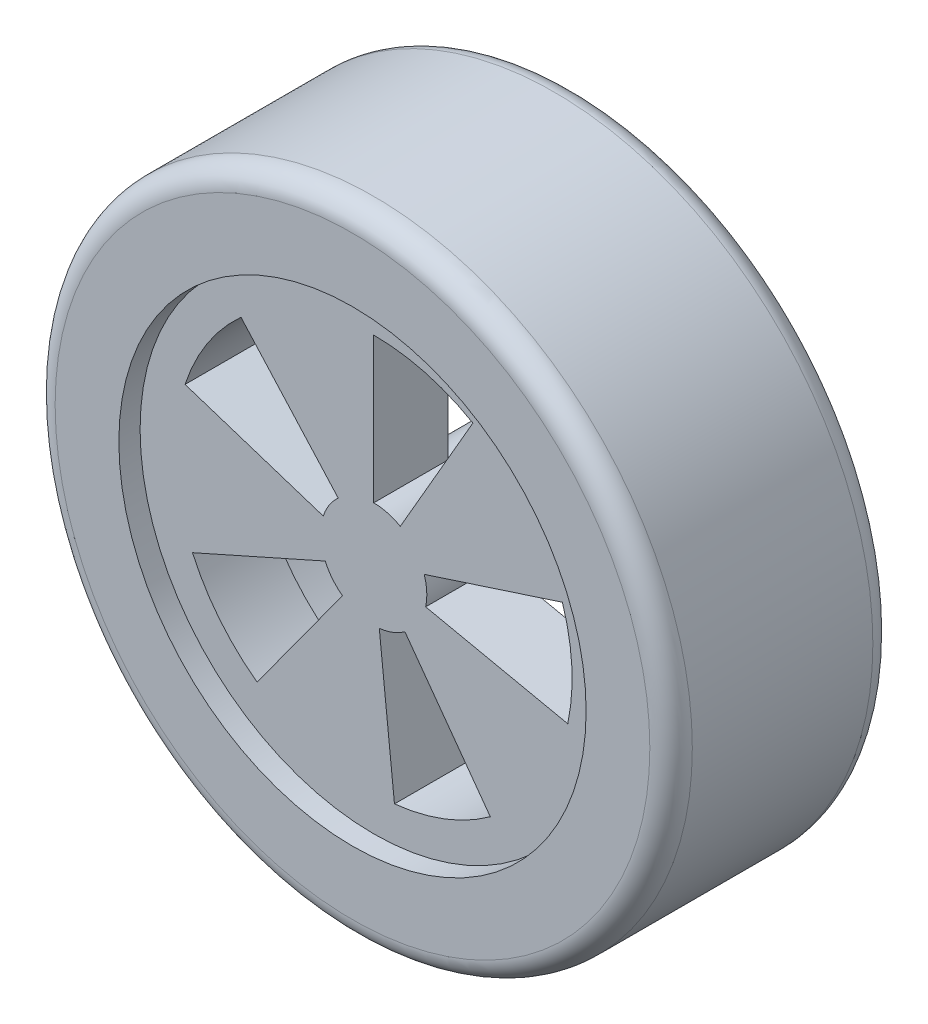
SolidWorks part; units mm, degrees
ref_plane "Front Plane" through (0, 0, 0) normal (0, 0, 1) x (1, 0, 0)
ref_plane "Top Plane" through (0, 0, 0) normal (0, 1, 0) x (1, 0, 0)
ref_plane "Right Plane" through (0, 0, 0) normal (1, 0, 0) x (0, 0, -1)
sketch "Sketch1" plane through (0, 0, 0) normal (0, 0, 1) x (1, 0, 0)
  circle A0 centre (0, 0) radius 15
extrude "Boss-Extrude1" add sketch "Sketch1" along normal blind 10.5 contours A0
sketch "Sketch2" plane through (0, 0, 10.5) normal (0, 0, 1) x (1, 0, 0)
  circle A0 centre (0, 0) radius 11
extrude "Cut-Extrude1" cut sketch "Sketch2" against normal blind 1
sketch "Sketch3" plane through (0, 0, 0) normal (0, 0, -1) x (-1, 0, 0)
  circle A0 centre (0, 0) radius 12
  circle A1 centre (0, 0) radius 2.5
  circle A2 centre (0, 0) radius 1
extrude "Cut-Extrude2" cut sketch "Sketch3" against normal blind 6 contours A0 A1 | A2 region at (11.6606, 0, 0) region at (0, 0, 0)
extrude "Boss-Extrude2" add sketch "Sketch3<4>" along normal blind 2.5 contours A1 A2 region at (2.4293, 0, 0)
sketch "Sketch3<4>" plane through (0, 0, 0) normal (0, 0, -1) x (-1, 0, 0) same geometry as "Sketch3"
fillet "Fillet1" radius 1 2 edges at (15, 0, 0) (15, 0, 10.5)
sketch "Sketch4" plane through (0, 0, 9.5) normal (0, 0, 1) x (1, 0, 0)
  line L0 (0, 2.5) -> (0, 9.3396)
  line L1 (1.25, 2.1651) -> (4.6698, 8.0883)
  line L2 (2.3776, 0.7725) -> (8.8825, 2.8861)
  line L3 (2.4454, -0.5198) -> (9.1355, -1.9418)
  line L4 (1.4695, -2.0225) -> (5.4897, -7.5559)
  line L5 (0.2613, -2.4863) -> (0.9763, -9.2884)
  line L6 (-1.4695, -2.0225) -> (-5.4897, -7.5559)
  line L7 (-2.2839, -1.0168) -> (-8.5322, -3.7988)
  line L8 (-2.3776, 0.7725) -> (-8.8825, 2.8861)
  line L9 (-1.6728, 1.8579) -> (-6.2494, 6.9407)
  arc A0 (4.6698, 8.0883) -> (0, 9.3396) centre (0, 0) ccw
  arc A2 (1.25, 2.1651) -> (0, 2.5) centre (0, 0) ccw
  arc A3 (9.1355, -1.9418) -> (8.8825, 2.8861) centre (0, 0) ccw
  arc A4 (2.4454, -0.5198) -> (2.3776, 0.7725) centre (0, 0) ccw
  arc A5 (0.9763, -9.2884) -> (5.4897, -7.5559) centre (0, 0) ccw
  arc A6 (0.2613, -2.4863) -> (1.4695, -2.0225) centre (0, 0) ccw
  arc A7 (-8.5322, -3.7988) -> (-5.4897, -7.5559) centre (0, 0) ccw
  arc A8 (-2.2839, -1.0168) -> (-1.4695, -2.0225) centre (0, 0) ccw
  arc A9 (-6.2494, 6.9407) -> (-8.8825, 2.8861) centre (0, 0) ccw
  arc A10 (-1.6728, 1.8579) -> (-2.3776, 0.7725) centre (0, 0) ccw
  point P3 (0, 0)
  point P9 (0, 0)
  point P14 (0, 0)
  point P19 (0, 0)
  point P24 (0, 0)
  point P29 (0, 0)
  dimension "D1" = 30
  dimension "D2" = 5
extrude "Cut-Extrude3" cut sketch "Sketch4" against normal through all
